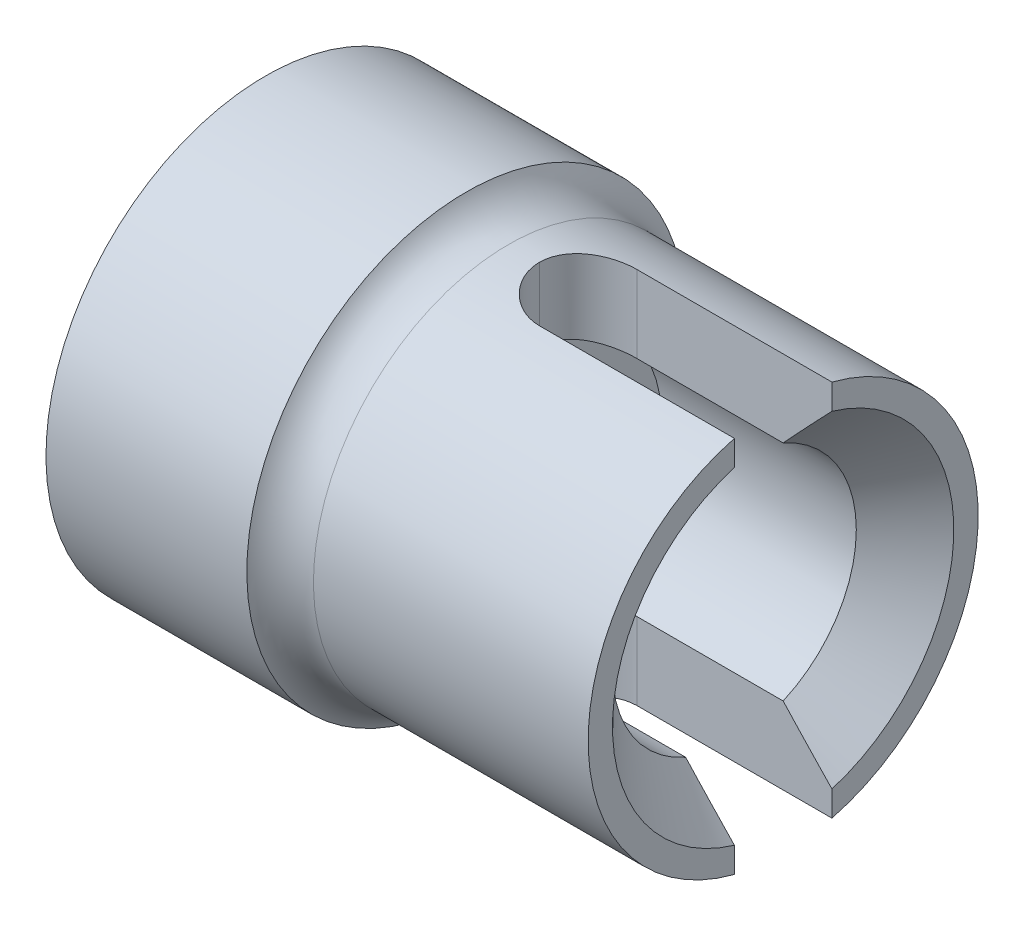
SolidWorks part; units mm, degrees
note: The reader was unsure of these and kept them because the rebuilt part matched: shared geometry of "Sketch3<3>", "Sketch3<4>".
material "Plain Carbon Steel"
ref_plane "Front" through (0, 0, 0) normal (0, 0, 1) x (1, 0, 0)
ref_plane "Top" through (0, 0, 0) normal (0, 1, 0) x (1, 0, 0)
ref_plane "Right" through (0, 0, 0) normal (1, 0, 0) x (0, 0, -1)
sketch "Sketch1" plane through (0, 0, 0) normal (0, 0, 1) x (1, 0, 0)
  line L1 (0, 0) -> (-25.4, 0)
  line L2 (0, 0) -> (0, 3.175)
  line L3 (0, 3.175) -> (-25.4, 3.175)
  line L4 (-25.4, 0) -> (-25.4, 3.175)
  line L5 (0, 0) -> (2.3813, 0)
  line L6 (0, 0) -> (0, 6.35)
  line L7 (0, 6.35) -> (2.3813, 6.35)
  line L8 (2.3813, 0) -> (2.3813, 6.35)
  line L9 (2.3813, 6.35) -> (10.3187, 6.35)
  line L10 (2.3813, 6.35) -> (2.3813, 3.9688)
  line L11 (2.3813, 3.9688) -> (10.3187, 3.9688)
  line L12 (10.3187, 6.35) -> (10.3187, 3.9688)
  line L13 (0, 3.175) -> (-1.5875, 3.175)
  line L14 (0, 3.175) -> (0, 4.7625)
  line L15 (0, 4.7625) -> (-1.5875, 4.7625)
  line L16 (-1.5875, 3.175) -> (-1.5875, 4.7625)
  point P11 (6.35, 3.9688)
  dimension "D1" = 3.175
  dimension "D2" = 25.4
  dimension "D3" = 6.35
  dimension "D4" = 2.3813
  dimension "D5" = 2.3813
  dimension "D6" = 4.7625
  dimension "D7" = 1.5875
  dimension "D8" = 7.9375
revolve "Revolve1" add sketch "Sketch1" angle 360 about L1
sketch "Sketch2" plane through (0, 0, 0) normal (0, 1, 0) x (1, 0, 0)
  line L0 (10.3187, -3.9688) -> (10.3187, 3.9688) construction
  line L1 (2.3813, -3.9688) -> (2.3813, 3.9688) construction
  line L2 (10.3187, -3.9688) -> (10.3187, 3.9688)
  line L3 (2.3813, -3.9688) -> (2.3813, 3.9688)
  line L4 (2.3813, 3.9688) -> (10.3187, 3.9688)
  line L5 (3.175, 1.5875) -> (3.175, -1.5875)
  line L6 (2.3813, -1.5875) -> (10.3187, -1.5875)
  line L7 (2.3813, -1.5875) -> (2.3813, 1.5875)
  line L8 (2.3813, 1.5875) -> (10.3187, 1.5875)
  line L9 (10.3187, -1.5875) -> (10.3187, 1.5875)
  line L10 (2.3813, -1.5875) -> (10.3187, 1.5875) construction
  line L11 (2.3813, 1.5875) -> (10.3187, -1.5875) construction
  circle A0 centre (6.35, 0) radius 1.5875
  point P6 (6.35, 3.9688)
  dimension "D1" = 3.175
  dimension "D2" = 0.7937
extrude "Cut-Extrude1" cut sketch "Sketch2" against normal through all both and the other way through all contours L8 L3 L6 L5 | A0 L8 L5 L6 | A0 | A0 L6 L2 L8
fillet "Fillet1" radius 1.5875 4 edges at (2.3813, -4.8929, -1.5875) (2.3813, 4.8929, -1.5875) (2.3813, -4.8929, 1.5875) (2.3813, 4.8929, 1.5875)
chamfer "Chamfer1" distance 1.5875 angle 45 2 edges at (10.3187, 0, -3.9688) (10.3187, 0, 3.9688)
sketch "Sketch3" plane through (0, 0, 0) normal (-1, 0, 0) x (0, 0, 1)
  line L0 (-5.0344, 5.5676) -> (-7.3389, 1.5761)
  line L1 (3.1778, -4.0208) -> (5.071, -0.7417)
  line L2 (5.071, 0.7417) -> (3.1778, 4.0208)
  line L3 (1.8932, 4.7625) -> (-1.8932, 4.7625)
  line L4 (-3.1778, 4.0208) -> (-5.071, 0.7417)
  line L5 (-5.071, -0.7417) -> (-3.1778, -4.0208)
  line L6 (-1.8932, -4.7625) -> (1.8932, -4.7625)
  line L7 (-7.3389, -1.5761) -> (-5.0344, -5.5676)
  line L8 (-2.3045, -7.1437) -> (2.3045, -7.1437)
  line L9 (5.0344, -5.5676) -> (7.3389, -1.5761)
  line L10 (7.3389, 1.5761) -> (5.0344, 5.5676)
  line L11 (2.3045, 7.1438) -> (-2.3045, 7.1438)
  circle A0 centre (0, 0) radius 2.286
  circle A1 centre (0, 0) radius 4.7625 construction
  arc A2 (-5.071, 0.7417) -> (-5.071, -0.7417) centre (0, 0) ccw
  arc A3 (-1.8932, 4.7625) -> (-3.1778, 4.0208) centre (0, 0) ccw
  arc A4 (3.1778, 4.0208) -> (1.8932, 4.7625) centre (0, 0) ccw
  arc A5 (5.071, -0.7417) -> (5.071, 0.7417) centre (0, 0) ccw
  arc A6 (1.8932, -4.7625) -> (3.1778, -4.0208) centre (0, 0) ccw
  arc A7 (-3.1778, -4.0208) -> (-1.8932, -4.7625) centre (0, 0) ccw
  arc A8 (-7.3389, 1.5761) -> (-7.3389, -1.5761) centre (0, 0) ccw
  arc A9 (-5.0344, -5.5676) -> (-2.3045, -7.1437) centre (0, 0) ccw
  arc A10 (2.3045, -7.1437) -> (5.0344, -5.5676) centre (0, 0) ccw
  arc A11 (7.3389, -1.5761) -> (7.3389, 1.5761) centre (0, 0) ccw
  arc A12 (5.0344, 5.5676) -> (2.3045, 7.1438) centre (0, 0) ccw
  arc A13 (-2.3045, 7.1438) -> (-5.0344, 5.5676) centre (0, 0) ccw
  circle A14 centre (0, 0) radius 7.1438
  circle M4 centre (0, 0) radius 6.35
  dimension "D1" = 4.572
  dimension "D3" = 10.25
  dimension "D2" = 9.525
  dimension "D4" = 2.3813
extrude "Cut-Extrude2" cut sketch "Sketch3" along normal through all contours L0 A8 L7 A9 L8 A10 L9 A11 L10 A12 L11 A13
extrude "Cut-Extrude3" cut sketch "Sketch3<3>" against normal through all contours A0
sketch "Sketch3<3>" plane through (0, 0, 0) normal (-1, 0, 0) x (0, 0, 1) same geometry as "Sketch3"
extrude "Boss-Extrude1" add sketch "Sketch3<4>" along normal blind 6.5405 contours L11 A13 L0 A8 L7 A9 L8 A10 L9 A11 L10 A12 M4 | A7 L5 A2 L4 A3 L3 A4 L2 A5 L1 A6 L6 M4
sketch "Sketch3<4>" plane through (0, 0, 0) normal (-1, 0, 0) x (0, 0, 1) same geometry as "Sketch3"
fillet "Fillet2" radius 1.5875 1 edges at (0, -6.35, 0)
